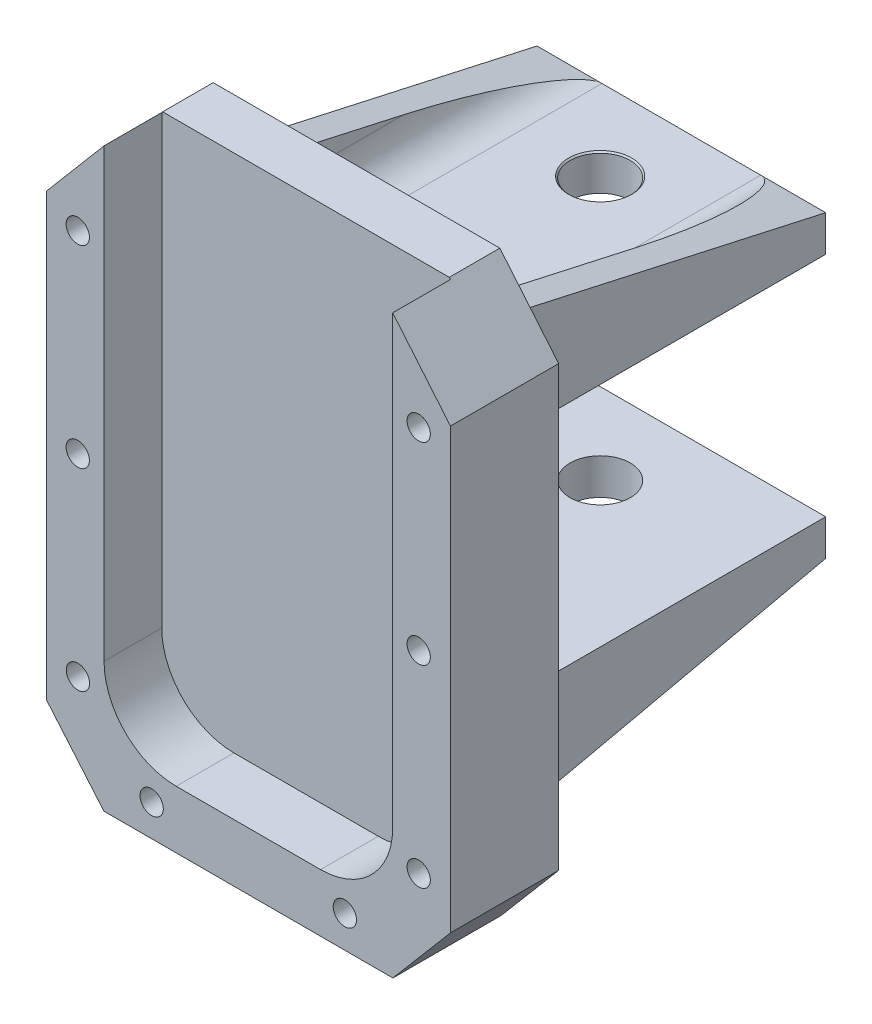
SolidWorks part; units mm, degrees
material "PET"
ref_plane "Front Plane" through (0, 0, 0) normal (0, 0, 1) x (1, 0, 0)
ref_plane "Top Plane" through (0, 0, 0) normal (0, 1, 0) x (1, 0, 0)
ref_plane "Right Plane" through (0, 0, 0) normal (1, 0, 0) x (0, 0, -1)
sketch "Sketch1" plane through (0, 0, 0) normal (0, 0, 1) x (1, 0, 0)
  line L1 (0, 0) -> (-35.56, 0)
  line L2 (0, 0) -> (0, 50.8)
  line L3 (0, 50.8) -> (-35.56, 50.8)
  line L4 (-35.56, 0) -> (-35.56, 50.8)
  dimension "D1" = 50.8
  dimension "D2" = 35.56
extrude "Boss-Extrude1" add sketch "Sketch1" along normal blind 9.525
sketch "Sketch2" plane through (0, 0, 9.525) normal (0, 0, 1) x (1, 0, 0)
  line L0 (0, 50.8) -> (-35.56, 50.8) construction
  line L1 (-30.48, 50.8) -> (-5.08, 50.8)
  line L2 (-30.48, 50.8) -> (-30.48, 5.08)
  line L3 (-30.48, 5.08) -> (-5.08, 5.08)
  line L4 (-5.08, 50.8) -> (-5.08, 5.08)
  line L5 (-35.56, 0) -> (0, 0) construction
  line L6 (-17.78, 0) -> (-17.78, 5.08) construction
  dimension "D1" = 45.72
  dimension "D2" = 25.4
extrude "Cut-Extrude2" cut sketch "Sketch2" against normal blind 5.08
hole_wizard "Tap Drill for M2.5x0.45 Tap1" positions "Sketch6" profile "Sketch5" hole size "M2.5x0.45" standard "ANSI Metric" end condition through all
sketch "Sketch6" plane through (0, 0, 0) normal (0, 0, -1) x (-1, 0, 0)
  point P0 (2.7924, 43.0871)
  point P2 (2.7924, 26.093)
  point P4 (2.7924, 9.1052)
  point P6 (9.2907, 2.8227)
  point P8 (26.2924, 2.7871)
  point P10 (32.78, 9.1052)
  point P12 (32.7924, 26.0871)
  point P14 (32.7924, 43.0871)
sketch "Sketch5" plane through (-2.7924, 43.0871, 0) normal (1, 0, 0) x (0, 1, 0)
  line L0 (0, 0) -> (0, 9.525)
  line L1 (0, 9.525) -> (1.025, 9.525)
  line L2 (1.025, 9.525) -> (1.025, 0)
  line L5 (1.025, 0) -> (0, 0)
  line L11 (0, -6.35) -> (0, 107.95) construction
  dimension "Thru Hole Dia." = 2.05
  dimension "Thru Hole Depth" = 9.525
sketch "Sketch13" plane through (0, 0, 0) normal (0, 0, -1) x (-1, 0, 0)
  line L0 (35.56, 0) -> (0, 0) construction
  line L1 (30.48, 39.265) -> (5.08, 39.265)
  line L2 (30.48, 39.265) -> (30.48, 36.09)
  line L3 (30.48, 36.09) -> (5.08, 36.09)
  line L4 (5.08, 39.265) -> (5.08, 36.09)
  line L5 (30.48, 39.265) -> (5.08, 36.09) construction
  line L6 (30.48, 36.09) -> (5.08, 39.265) construction
  line L7 (30.48, 16.09) -> (5.08, 16.09)
  line L8 (30.48, 16.09) -> (30.48, 12.915)
  line L9 (30.48, 12.915) -> (5.08, 12.915)
  line L10 (5.08, 16.09) -> (5.08, 12.915)
  line L11 (30.48, 16.09) -> (5.08, 12.915) construction
  line L12 (30.48, 12.915) -> (5.08, 16.09) construction
  line L13 (17.78, 16.09) -> (17.78, 36.09) construction
  line L15 (0, 50.8) -> (35.56, 50.8) construction
  point P0 (17.78, 37.6775)
  point P5 (17.78, 14.5025)
  point P12 (17.78, 0)
  point P15 (17.78, 26.09)
  dimension "D1" = 3.175
  dimension "D2" = 3.175
  dimension "D3" = 25.4
  dimension "D4" = 20
  dimension "D5" = 24.71
extrude "Boss-Extrude2" add sketch "Sketch13" along normal blind 28.575
sketch "Sketch8" plane through (0, 0, 9.525) normal (0, 0, 1) x (1, 0, 0)
  line L0 (-5.179, 50.8) -> (0, 44.5915)
  line L1 (-5.08, 50.8) -> (-30.48, 50.8) construction
  line L2 (0, 0) -> (0, 50.8) construction
  line L3 (0.0027, 44.5883) -> (-5.0973, 50.5883) construction
  line L4 (0, 44.5915) -> (0, 50.8)
  line L5 (0, 50.8) -> (-5.179, 50.8)
  line L6 (-35.56, 44.7066) -> (-35.56, 50.8)
  line L7 (-35.56, 50.8) -> (-35.56, 0) construction
  line L8 (-35.56, 50.8) -> (-30.4026, 50.8)
  line L9 (-30.4026, 50.8) -> (-35.56, 44.7066)
  line L10 (-35.56, 5.97) -> (-35.56, 0)
  line L11 (-35.56, 0) -> (-30.4926, 0)
  line L12 (-35.56, 0) -> (0, 0) construction
  line L13 (-30.4926, 0) -> (-35.56, 5.97)
  line L14 (-5.0926, -0.0313) -> (0, 0)
  line L15 (0, 0) -> (0, 5.97)
  line L16 (0, 5.97) -> (-5.0926, -0.0313)
extrude "Cut-Extrude3" cut sketch "Sketch8" against normal through all
ref_plane "Plane6" through (-23.56, 0, 0) normal (-1, 0, 0) x (0, 0, 1)
fillet "Fillet1" radius 6.35 2 edges at (-5.08, 5.08, 6.985) (-30.48, 5.08, 6.985)
sketch "Sketch10" plane through (-43.87, 39.265, 0) normal (0, -1, 0) x (0, 0, -1)
  line L2 (14.2875, 13.39) -> (14.2875, 38.79) construction
  line L3 (0, 38.79) -> (0, 13.39) construction
  line L4 (14.2875, 26.09) -> (0, 26.09) construction
  line L6 (28.575, 13.39) -> (0, 13.39) construction
  line L7 (28.575, 38.79) -> (0, 38.79) construction
  line L8 (14.2875, 26.09) -> (28.575, 26.09) construction
  line L9 (28.575, 38.79) -> (28.575, 13.39) construction
  circle A0 centre (21.4312, 26.09) radius 3.175
  circle A1 centre (7.1438, 26.09) radius 3.175
  dimension "D1" = 6.35
hole_wizard "M5 Clearance Hole1" positions "3DSketch1" profile "Sketch11" hole size "M5" standard "ANSI Metric" end condition through all
sketch3d "3DSketch1"
  point P0 (-17.78, 39.265, -7.1438)
  point P3 (-17.78, 39.265, -21.4312)
  point P6 (0, 0, 0)
sketch "Sketch11" plane through (-17.78, 39.265, -7.1438) normal (1, 0, 0) x (0, 0, 1)
  line L0 (0, 0) -> (0, 39.265)
  line L1 (0, 39.265) -> (2.65, 39.265)
  line L2 (2.65, 39.265) -> (2.65, 0.125)
  line L3 (2.65, 0.125) -> (2.775, 0)
  line L5 (2.775, 0) -> (0, 0)
  line L6 (-2.65, 0.125) -> (-2.775, 0) construction
  line L11 (0, -6.35) -> (0, 107.95) construction
  dimension "Thru Hole Dia." = 5.3
  dimension "Thru Hole Depth" = 39.265
  dimension "Near C'Sink Dia." = 5.55
  dimension "Near C'Sink Angle" = 90
sketch "Sketch14" plane through (-30.48, 0, 0) normal (-1, 0, 0) x (0, 0, 1)
  line L0 (-28.575, 12.915) -> (0, 6.565)
  line L1 (0, 44.7066) -> (0, 5.97) construction
  line L2 (-28.575, 12.915) -> (0, 12.915) construction
  dimension "D1" = 6.35
rib "Rib7" sketch "Sketch14" sketch "Sketch14" thickness 2.54 extrusion direction parallel to sketch draft on no parameters "D1"=2.54
sketch "Sketch15" plane through (-5.08, 0, 0) normal (1, 0, 0) x (0, 0, -1)
  line L0 (28.575, 12.915) -> (0, 6.565)
rib "Rib8" sketch "Sketch15" sketch "Sketch15" thickness 2.54 extrusion direction parallel to sketch draft on no parameters "D1"=2.54
sketch "Sketch16" plane through (-30.48, 0, 0) normal (-1, 0, 0) x (0, 0, 1)
  line L0 (-28.575, 39.265) -> (0, 45.615)
  line L1 (0, 44.7066) -> (0, 5.97) construction
  dimension "D1" = 6.35
sketch "Sketch17" plane through (-5.08, 0, 0) normal (1, 0, 0) x (0, 0, -1)
  line L0 (28.575, 39.265) -> (0, 45.615)
rib "Rib9" sketch "Sketch17" sketch "Sketch17" thickness 2.54 extrusion direction parallel to sketch draft on no parameters "D1"=2.54
rib "Rib10" sketch "Sketch16" sketch "Sketch16" thickness 2.54 extrusion direction parallel to sketch draft on no parameters "D1"=2.54
fillet "Fillet2" radius 3.175 2 edges at (-27.94, 12.915, -14.2875) (-7.62, 12.915, -14.2875)
fillet "Fillet3" radius 3.175 2 edges at (-7.62, 39.265, -14.2875) (-27.94, 39.265, -14.2875)
sketch "Sketch18" plane through (0, 39.265, 0) normal (0, 1, 0) x (1, 0, 0)
  line L0 (-17.78, 7.1438) -> (-17.78, 21.4312) construction
